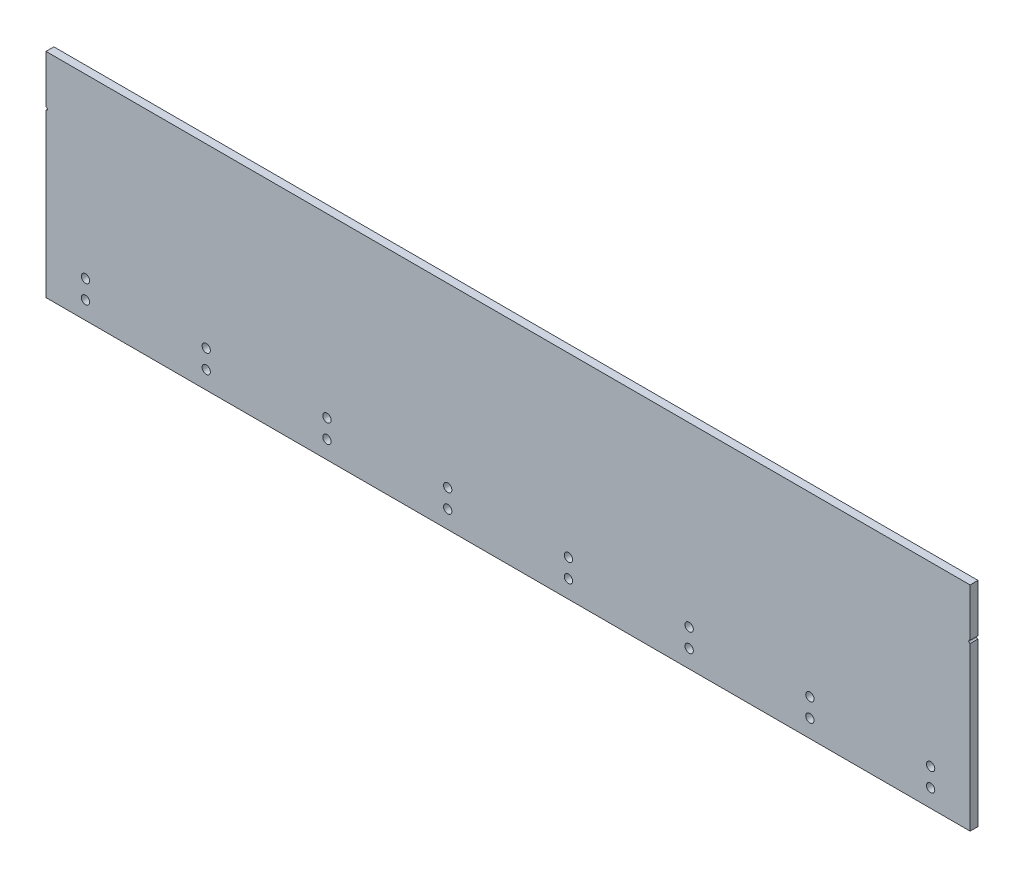
SolidWorks part; units mm, degrees
note: The reader was unsure of these and kept them because the rebuilt part matched: thickness of "Taban-Flanş1", "Sac-Levha1".
ref_plane "Ön Düzlem" through (0, 0, 0) normal (0, 0, 1) x (1, 0, 0)
ref_plane "Üst Düzlem" through (0, 0, 0) normal (0, 1, 0) x (1, 0, 0)
ref_plane "Sağ Düzlem" through (0, 0, 0) normal (1, 0, 0) x (0, 0, -1)
sketch "Çizim1" plane through (0, 0, 0) normal (0, 0, 1) x (1, 0, 0)
  line L0 (0, 415) -> (2340, 415) construction
  line L1 (0, 0) -> (2340, 0)
  line L2 (0, 0) -> (0, 411.5)
  line L3 (0, 540) -> (2340, 540)
  line L4 (2340, 0) -> (2340, 411.5)
  line L5 (0, 418.5) -> (0, 540)
  line L6 (2340, 418.5) -> (2340, 540)
  circle A0 centre (100, 92) radius 10.5
  circle A1 centre (100, 45) radius 10.5
  circle A2 centre (405.7143, 92) radius 10.5
  circle A3 centre (405.7143, 45) radius 10.5
  circle A4 centre (711.4286, 92) radius 10.5
  circle A5 centre (711.4286, 45) radius 10.5
  circle A6 centre (1017.1429, 92) radius 10.5
  circle A7 centre (1017.1429, 45) radius 10.5
  circle A8 centre (1322.8571, 92) radius 10.5
  circle A9 centre (1322.8571, 45) radius 10.5
  circle A10 centre (1628.5714, 92) radius 10.5
  circle A11 centre (1628.5714, 45) radius 10.5
  circle A12 centre (1934.2857, 92) radius 10.5
  circle A13 centre (1934.2857, 45) radius 10.5
  circle A14 centre (2240, 92) radius 10.5
  circle A15 centre (2240, 45) radius 10.5
  arc A16 (0, 411.5) -> (0, 418.5) centre (0, 415) ccw
  arc A17 (2340, 418.5) -> (2340, 411.5) centre (2340, 415) ccw
  dimension "D4" = 21
  dimension "D8" = 100
  dimension "D9" = 7
  dimension "D1" = 2340
  dimension "D2" = 540
  dimension "D3" = 47
  dimension "D5" = 100
  dimension "D6" = 45
  dimension "D10" = 125
  dimension "D11" = 305.7143
  dimension "D12" = 305.7143
  dimension "D13" = 305.7143
  dimension "D14" = 305.7143
  dimension "D15" = 305.7143
  dimension "D16" = 305.7143
  dimension "D17" = 305.7143
  dimension "D7" = 8
base flange "Taban-Flanş1" sketch "Çizim1" thickness 20 reverse thickness direction no parameters "D1"=8
sketch "Büküm-Çizgileri1" [suppressed] plane through (0, 0, 0) normal (0, 1, 0) x (1, 0, 0)
sketch "Sınırlandırma-Kutusu1" [suppressed] plane through (0, 0, 0) normal (0, 1, 0) x (1, 0, 0)
sheet metal parameters "Sac-Levha1" thickness 20 parameters "D1"=8
flat pattern "Düz-Çoğaltma1" [suppressed]
sketch "Büküm-Çizgileri2" plane through (0, 0, 0) normal (0, 1, 0) x (1, 0, 0)
sketch3d "Sınırlandırma-Kutusu2" [suppressed]
  line L0 (0, -415, 0) -> (2340, -415, 0) construction
  line L1 (0, 125, 0) -> (2340, 125, 0) construction
  line L2 (0, -415, 0) -> (0, 125, 0) construction
  line L3 (2340, -415, 0) -> (2340, 125, 0) construction
